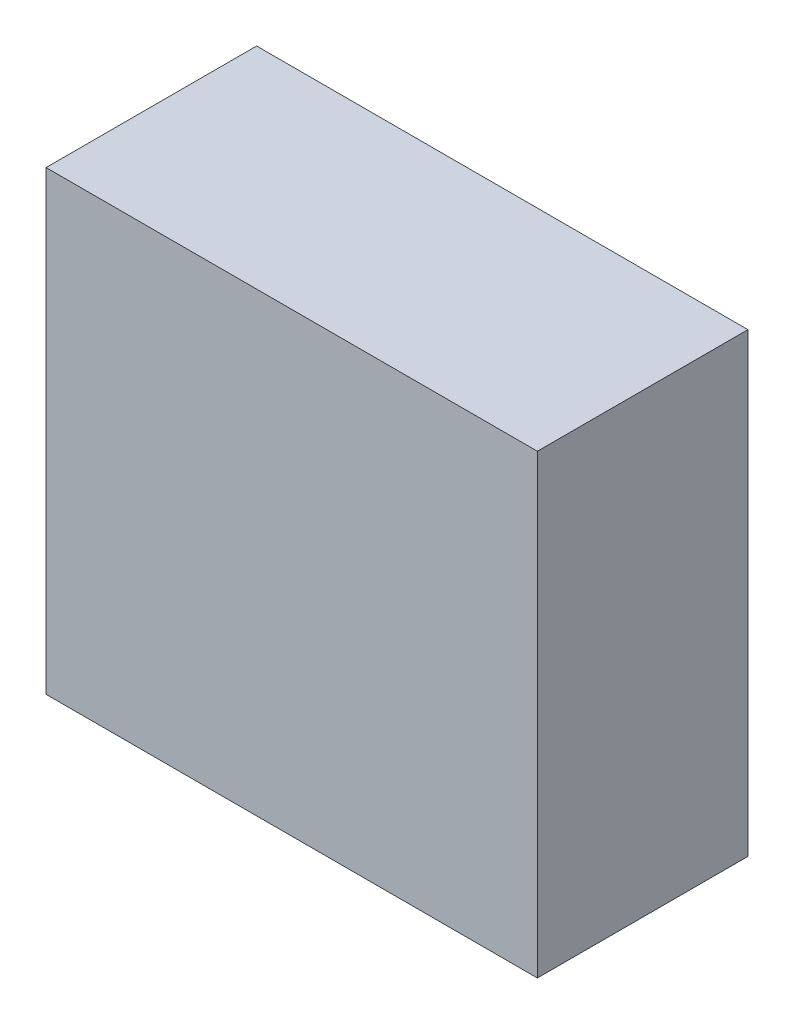
SolidWorks part; units mm, degrees
ref_plane "Front Plane" through (0, 0, 0) normal (0, 0, 1) x (1, 0, 0)
ref_plane "Top Plane" through (0, 0, 0) normal (0, 1, 0) x (1, 0, 0)
ref_plane "Right Plane" through (0, 0, 0) normal (1, 0, 0) x (0, 0, -1)
sketch "Sketch1" plane through (0, 0, 0) normal (0, 1, 0) x (1, 0, 0)
  line L0 (-88.9, 38.1) -> (88.9, -38.1) construction
  line L1 (-88.9, 38.1) -> (88.9, 38.1)
  line L2 (-88.9, 38.1) -> (-88.9, -38.1)
  line L3 (-88.9, -38.1) -> (88.9, -38.1)
  line L4 (88.9, 38.1) -> (88.9, -38.1)
  dimension "D1" = 177.8
  dimension "D2" = 76.2
extrude "Boss-Extrude1" add sketch "Sketch1" along normal mid plane 165.1
